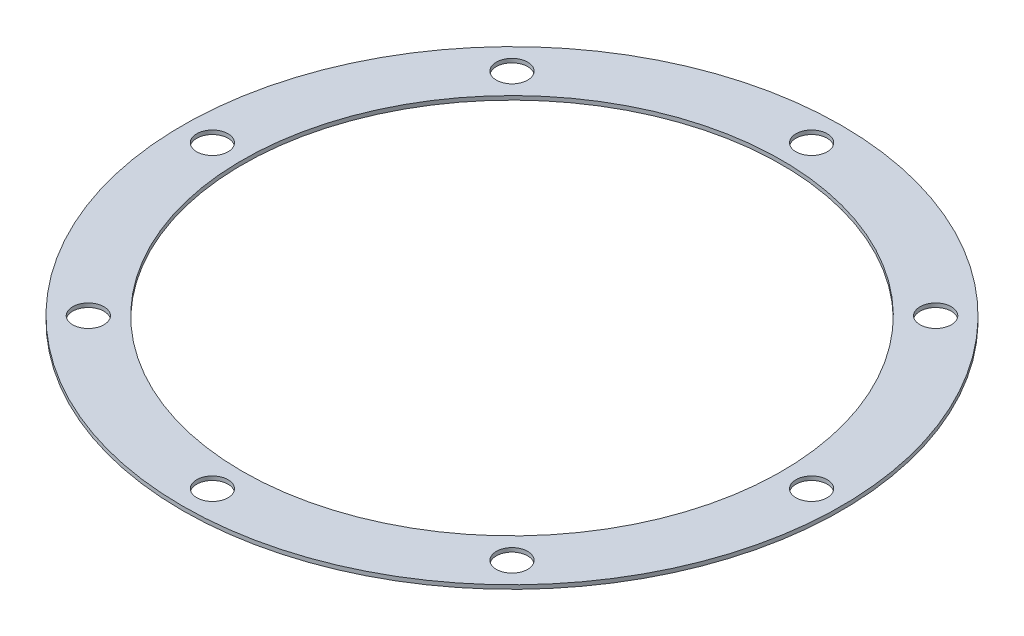
SolidWorks part; units mm, degrees
ref_plane "Front Plane" through (0, 0, 0) normal (0, 0, 1) x (1, 0, 0)
ref_plane "Top Plane" through (0, 0, 0) normal (0, 1, 0) x (1, 0, 0)
ref_plane "Right Plane" through (0, 0, 0) normal (1, 0, 0) x (0, 0, -1)
sketch "Sketch1" plane through (0, 0, 0) normal (0, 1, 0) x (1, 0, 0)
  circle A0 centre (0, 0) radius 69.85
  circle A1 centre (0, 0) radius 57.15
  dimension "D1" = 139.7
  dimension "D2" = 114.3
extrude "Boss-Extrude1" add sketch "Sketch1" along normal blind 0.8382
sketch "Sketch2" plane through (0, 0.8382, 0) normal (0, 1, 0) x (1, 0, 0)
  line L0 (0, 0) -> (0, 63.5) construction
  circle A0 centre (0, 63.5) radius 3.3147
  dimension "D2" = 6.6294
  dimension "D1" = 63.5
extrude "Cut-Extrude1" cut sketch "Sketch2" against normal blind 2.54
ref_axis "Axis1" through (0, -0.0419, 0) along (0, 1, 0)
pattern_circular "CirPattern1" count 8 over 360 about axis through (0, -0.0419, 0) along (0, 1, 0) of "Cut-Extrude1"
